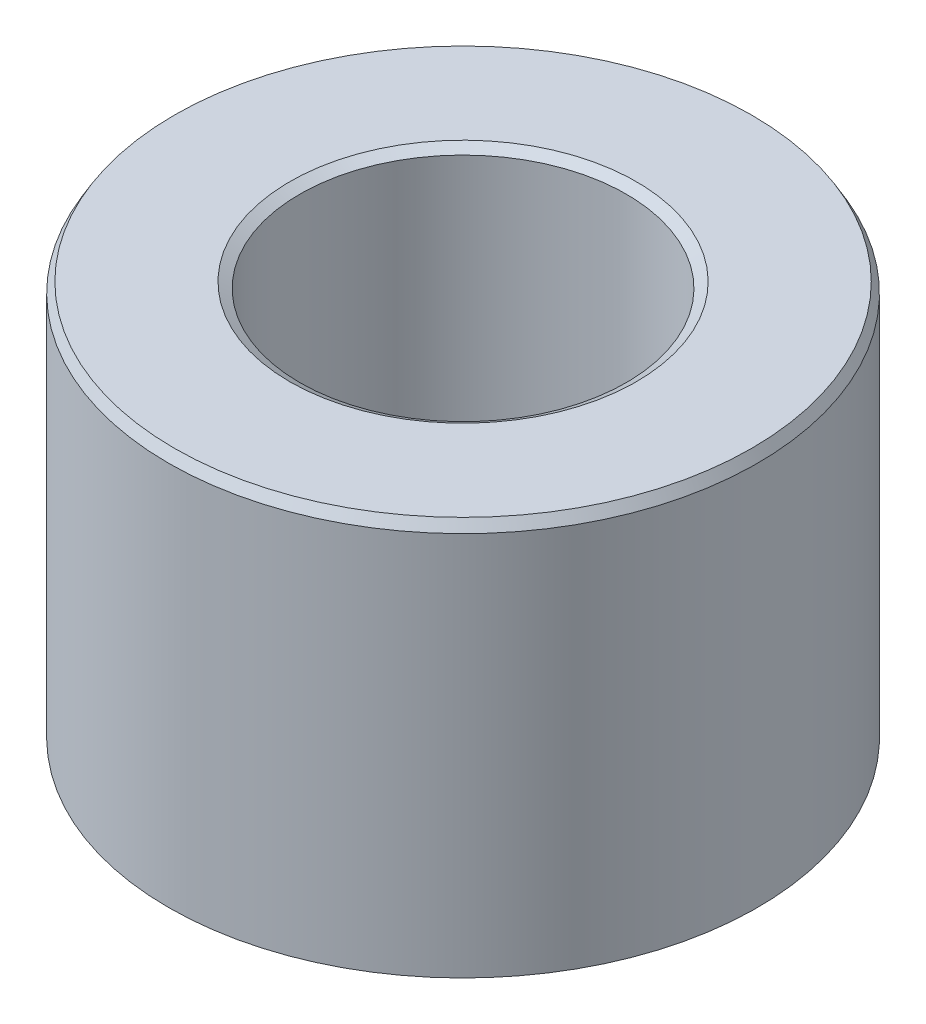
SolidWorks part; units mm, degrees
ref_plane "Front Plane" through (0, 0, 0) normal (0, 0, 1) x (1, 0, 0)
ref_plane "Top Plane" through (0, 0, 0) normal (0, 1, 0) x (1, 0, 0)
ref_plane "Right Plane" through (0, 0, 0) normal (1, 0, 0) x (0, 0, -1)
sketch "Sketch1" plane through (0, 0, 0) normal (0, 1, 0) x (1, 0, 0)
  circle A0 centre (0, 0) radius 50
  dimension "SLEEVE_OD" = 100
extrude "Boss-Extrude1" add sketch "Sketch1" along normal blind 68.0298
sketch "Sketch2" plane through (0, 0, 0) normal (0, 1, 0) x (1, 0, 0)
  circle A0 centre (0, 0) radius 27.7278
  dimension "BORE_D" = 55.4556
extrude "Cut-Extrude1" cut sketch "Sketch2" along normal through all
chamfer "Chamfer1" distance 1.7032 angle 30 4 edges at (0, 68.0298, 27.7278) (0, 0, 27.7278) (0, 0, 50) (0, 68.0298, 50) first distance on face at (0, 68.0298, 27.7278) first distance on face at (0, 0, 27.7278) first distance on face at (0, 68.0298, 50)
